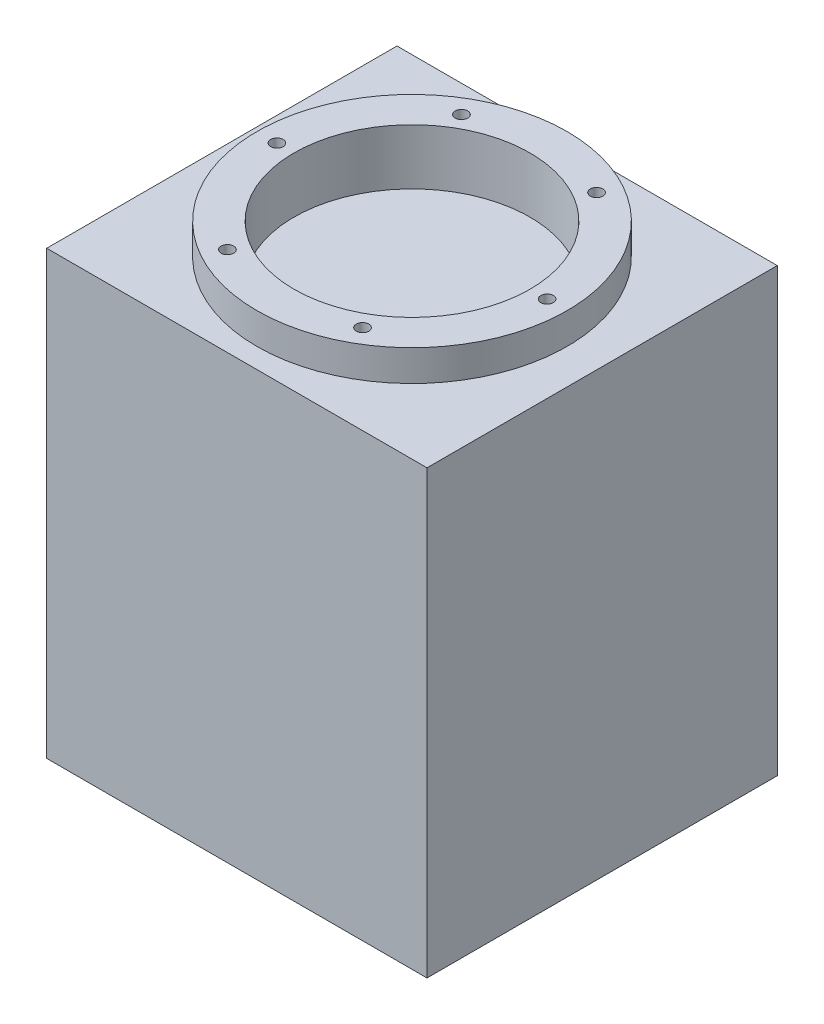
SolidWorks part; units mm, degrees
ref_plane "Front Plane" through (0, 0, 0) normal (0, 0, 1) x (1, 0, 0)
ref_plane "Top Plane" through (0, 0, 0) normal (0, 1, 0) x (1, 0, 0)
ref_plane "Right Plane" through (0, 0, 0) normal (1, 0, 0) x (0, 0, -1)
sketch "Sketch1" plane through (0, 0, 0) normal (0, 1, 0) x (1, 0, 0)
  line L1 (-38, -35) -> (38, -35)
  line L2 (-38, -35) -> (-38, 35)
  line L3 (-38, 35) -> (38, 35)
  line L4 (38, -35) -> (38, 35)
  line L5 (-38, -35) -> (38, 35) construction
  line L6 (-38, 35) -> (38, -35) construction
  point P0 (0, 0)
  dimension "D1" = 76
  dimension "D2" = 70
extrude "Boss-Extrude1" add sketch "Sketch1" along normal blind 88.3
sketch "Sketch2" plane through (0, 88.3, 0) normal (0, 1, 0) x (1, 0, 0)
  circle A0 centre (0, 0) radius 31
  dimension "D1" = 62
extrude "Boss-Extrude2" add sketch "Sketch2" along normal blind 6.2
sketch "Sketch3" plane through (0, 94.5, 0) normal (0, 1, 0) x (1, 0, 0)
  circle A0 centre (0, 0) radius 27 construction
  dimension "D1" = 54
hole_wizard "M3x0.5 Tapped Hole3" positions "Sketch6" profile "Sketch7" tap size "M3x0.5" standard "ANSI Metric"
sketch "Sketch6" plane through (0, 94.5, 0) normal (0, 1, 0) x (1, 0, 0)
  circle A0 centre (0, 0) radius 27 construction
  point P0 (27, 0)
cosmetic thread "Hole Thread1" parameters "D1"=5, "D2"=3
sketch "Sketch7" plane through (27, 94.5, 0) normal (1, 0, 0) x (0, 0, 1)
  line L0 (0, 0) -> (0, 7.2511)
  line L1 (0, 7.2511) -> (1.25, 6.5)
  line L2 (1.25, 6.5) -> (1.25, 0)
  line L5 (1.25, 0) -> (0, 0)
  line L10 (0, 7.2511) -> (-1.25, 6.5) construction
  line L11 (0, -6.35) -> (0, 107.95) construction
  dimension "Tap Drill Dia." = 2.5
  dimension "Tap Drill Depth" = 6.5
  dimension "Drill Angle" = 118
ref_axis "Axis1" through (0, 112.5828, 0) along (0, -1, 0)
pattern_circular "CirPattern1" count 6 over 360 about axis through (0, 112.5828, 0) along (0, -1, 0) of "M3x0.5 Tapped Hole3"
cosmetic thread "Hole Thread2" parameters "D1"=5, "D2"=3
cosmetic thread "Hole Thread3" parameters "D1"=5, "D2"=3
cosmetic thread "Hole Thread4" parameters "D1"=5, "D2"=3
cosmetic thread "Hole Thread5" parameters "D1"=5, "D2"=3
cosmetic thread "Hole Thread6" parameters "D1"=5, "D2"=3
sketch "Sketch8" plane through (0, 94.5, 0) normal (0, 1, 0) x (1, 0, 0)
  circle A0 centre (0, 0) radius 23.5888
extrude "Cut-Extrude1" cut sketch "Sketch8" against normal blind 11.11
ref_plane "Chip plane" through (0, 83.39, 0) normal (0, 1, 0) x (1, 0, 0)
ref_point "Point1"
